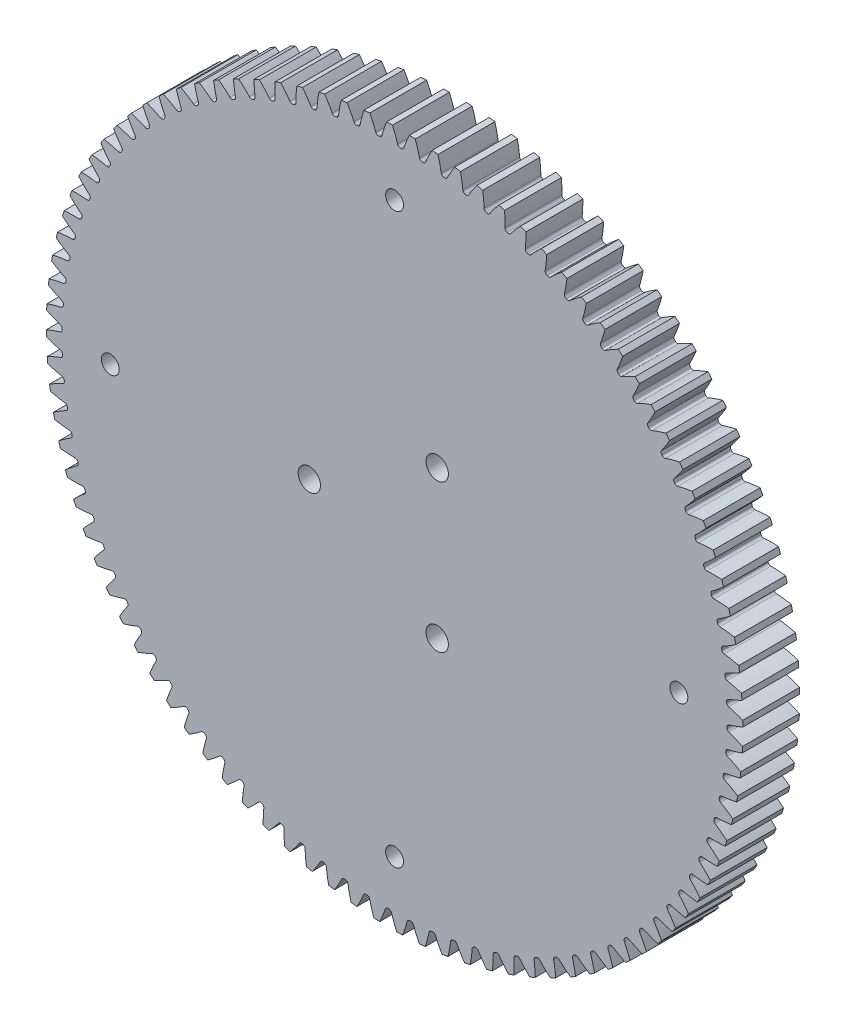
SolidWorks part; units mm, degrees
ref_plane "Front" through (0, 0, 0) normal (0, 0, 1) x (1, 0, 0)
ref_plane "Top" through (0, 0, 0) normal (0, 1, 0) x (1, 0, 0)
ref_plane "Right" through (0, 0, 0) normal (1, 0, 0) x (0, 0, -1)
sketch "Sketch3" plane through (0, 0, 0) normal (0, 0, 1) x (1, 0, 0)
  circle A0 centre (0, 0) radius 77.7875
  dimension "od" = 155.575
extrude "gearBody" add sketch "Sketch3" along normal blind 12.7
sketch "Sketch2" plane through (0, 0, 0) normal (0, 0, 1) x (1, 0, 0)
  line L0 (0, 0) -> (66.154, 27.4019) construction
  line L1 (89.9379, -14.1817) -> (0, 0) construction
  line L2 (0, 0) -> (36.3143, 0) construction
  line L3 (76.1998, -0.172) -> (76.1546, -2.6294) construction
  line L5 (76.1772, -1.4007) -> (0, 0) construction
  line L7 (0, 0) -> (71.6046, 0) construction
  arc A0 (71.5902, -1.4371) -> (71.5946, -1.1957) centre (0, 0) ccw construction
  arc A1 (77.7861, 0.4588) -> (77.7167, -3.3181) centre (0, 0) ccw construction
  arc A2 (76.1998, -0.172) -> (76.1546, -2.6294) centre (0, 0) ccw construction
  arc A3 (74.2296, -1.47) -> (74.2335, -1.2598) centre (0, 0) ccw
  arc A4 (89.9379, -14.1817) -> (74.6441, -2.0632) centre (65.1019, -29.8153) ccw
  arc A5 (89.9379, -14.1817) -> (90.3984, 10.8657) centre (0, 0) ccw
  arc A6 (90.3984, 10.8657) -> (74.6695, -0.6823) centre (66.154, 27.4019) cw
  arc A7 (74.2335, -1.2598) -> (74.6695, -0.6823) centre (74.8478, -1.2702) cw
  arc A8 (74.6441, -2.0632) -> (74.2296, -1.47) centre (74.8439, -1.4822) cw
  point P6 (90.3984, 10.8657)
  point P22 (89.9379, -14.1817)
  dimension "baseDia" = 143.2092
  dimension "od" = 155.575
  dimension "pd" = 152.4
  dimension "rd" = 148.4884
  dimension "rFillet" = 0.6144
  dimension "pointX" = 90.3984
  dimension "pointY" = 10.8657
  dimension "CTT" = 2.4574
  dimension "flankCenterAngle" = 22.5
extrude "toothCut" cut sketch "Sketch2" along normal through all
pattern_circular "CirPattern1" count 96 over 360 about axis through (0, 0, 12.7) along (0, 0, -1) of "toothCut"
sketch "hub1Dia" plane through (0, 0, 0) normal (0, 0, -1) x (-1, 0, 0)
  circle A0 centre (0, 0) radius 12.7
  dimension "hub1Dia" = 25.4
sketch "hub2Dia" plane through (0, 0, 12.7) normal (0, 0, 1) x (1, 0, 0)
  circle A0 centre (0, 0) radius 12.7
  dimension "hub2dia" = 25.4
sketch "boreDia" plane through (0, 0, 0) normal (0, 0, 1) x (1, 0, 0)
  circle A0 centre (0, 0) radius 7.9375
  dimension "boreDia" = 15.875
sketch "Sketch4" plane through (0, 0, 0) normal (0, 0, -1) x (-1, 0, 0)
  circle A0 centre (19.05, 0) radius 2.5
  circle A1 centre (-9.525, -16.4978) radius 2.5
  circle A2 centre (-9.525, 16.4978) radius 2.5
  point P10 (0, 0)
  dimension "D2" = 5
  dimension "D1" = 19.05
  dimension "D3" = 3
extrude "Cut-Extrude1" cut sketch "Sketch4" against normal through all
sketch "Sketch5" plane through (0, 0, 0) normal (0, 0, -1) x (-1, 0, 0)
  circle A0 centre (63.5, 0) radius 2
  circle A1 centre (0, -63.5) radius 2
  circle A2 centre (-63.5, 0) radius 2
  circle A3 centre (0, 63.5) radius 2
  point P12 (0, 0)
  dimension "D1" = 4
  dimension "D2" = 63.5
  dimension "D3" = 4
extrude "Cut-Extrude2" cut sketch "Sketch5" against normal through all
equation "\"D2@Sketch4\"=5mm"
equation "\"D1@Sketch5\"=4mm"
